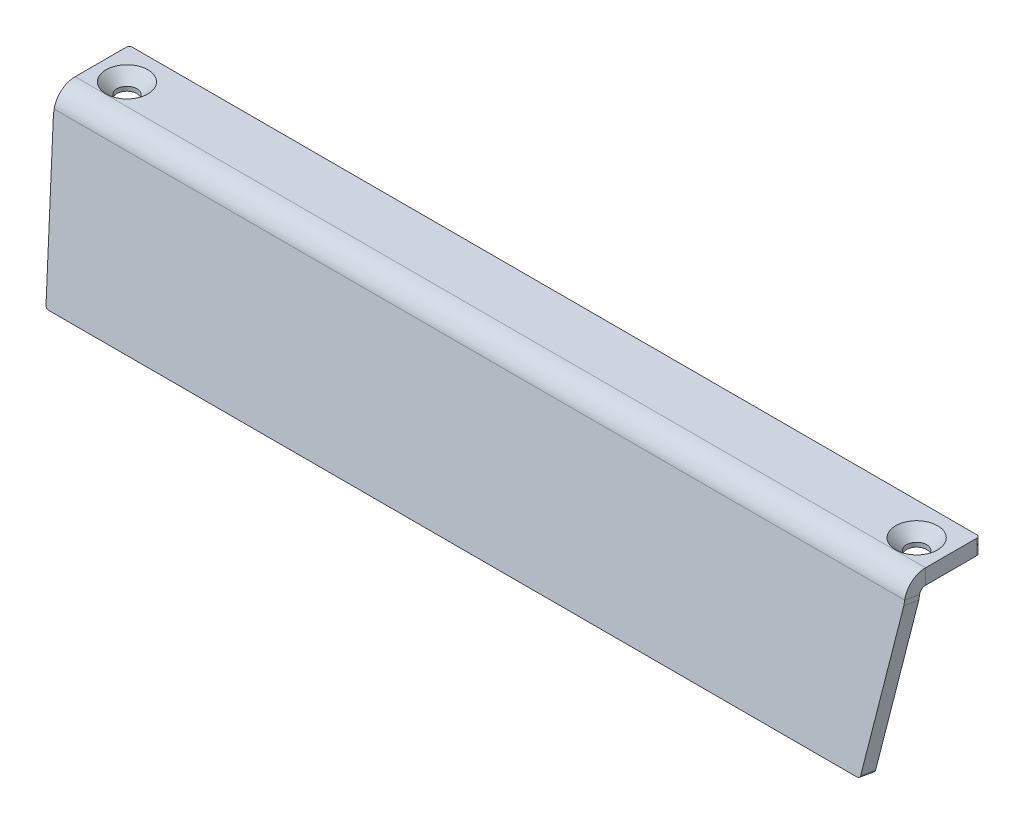
SolidWorks part; units mm, degrees
note: '?' marks a value the reader was unsure of. The reader was unsure of these and kept them because the rebuilt part matched: thickness of "Base-Flange1", "Edge-Flange1", "Sheet-Metal(1)", "Sheet-Metal(2)", "Sheet-Metal(10)", "Sheet-Metal(11)", "Sheet-Metal(12)"; flange length of "Edge-Flange1".
ref_plane "Front" through (0, 0, 0) normal (0, 0, 1) x (1, 0, 0)
ref_plane "Top" through (0, 0, 0) normal (0, 1, 0) x (1, 0, 0)
ref_plane "Right" through (0, 0, 0) normal (1, 0, 0) x (0, 0, -1)
sketch "Sketch1" plane through (0, 0, 0) normal (0, 1, 0) x (1, 0, 0)
  line L0 (-50, 0) -> (50, 0) construction
  line L1 (-70, 0) -> (70, 0)
  line L2 (-70, 0) -> (-70, -8.92)
  line L3 (-70, -8.92) -> (70, -8.92)
  line L4 (70, 0) -> (70, -8.92)
  line L5 (0, 0) -> (0, -26.7104) construction
  line L6 (0, -50) -> (0, 50) construction
  dimension "D1" = 8.92
  dimension "D2" = 140
base flange "Base-Flange1" sketch "Sketch1" thickness 2.5 reverse thickness direction no parameters "D1"=1.524
edge flange "Edge-Flange1" sketch "Sketch8" flange angle 100 flange length 26 flange position bend outside bend radius 1 thickness 2.5 relief rectangular parameters "D6"=10
sketch "Sketch8" plane through (0, -2.5, 8.92) normal (0, 0.1736, 0.9848) x (-1, 0, 0)
  line L0 (70, 0) -> (-70, 0) construction
  line L1 (70, 0) -> (-70, 0)
  line L2 (-70, 0) -> (-70, 26)
  line L3 (-70, 26) -> (70, 26)
  line L4 (70, 26) -> (70, 0)
bend "EdgeBend1" bend radius 1 bend angle 80 parameters "D5"=1
sketch "Sketch21" plane through (0, 0, 0) normal (0, 1, 0) x (1, 0, 0)
  line L0 (0, 0) -> (0, -13.0774) construction
  line L1 (0, -50) -> (0, 50) construction
  line L2 (-65, -5.39) -> (65, -5.39) construction
  circle A0 centre (-65, -5.39) radius 1.65
  circle A1 centre (65, -5.39) radius 1.65
  dimension "D1" = 3.3
  dimension "D2" = 130
  dimension "D3" = 5.39
ref_plane "Plane1" through (65, 0, 0) normal (1, 0, 0) x (0, 0, -1)
extrude "Cut-Extrude1" cut sketch "Sketch21" against normal through all normal cut yes
ref_axis "Axis2" through (65, -2.5, 5.39) along (0, 1, 0)?
sketch "Sketch24" plane through (65, 0, 0) normal (1, 0, 0) x (0, 0, -1)
  line L0 (-5.39, 0) -> (-5.39, 4.9908) construction
  line L1 (-8.92, 0) -> (0, 0) construction
  line L2 (-5.39, 0) -> (-5.39, -1.8)
  line L3 (-5.39, -1.8) -> (-3.74, -1.8)
  line L4 (-3.74, -1.8) -> (-1.94, 0)
  line L5 (-1.94, 0) -> (-5.39, 0)
  dimension "D1" = 5.39
  dimension "D2" = 45
  dimension "D3" = 1.8
  dimension "D4" = 1.65
revolve "Cut-Revolve2" cut sketch "Sketch24" angle 360 about L0
mirror "Mirror2" about plane through (0, 0, 0) normal (1, 0, 0) of "Cut-Revolve2"
chamfer "Chamfer1" distance 3 angle 83 2 edges at (-70, -27.8879, 15.505) (70, -27.8879, 15.505) first distance on face at (0, -27.8879, 15.505)
fillet "Fillet1" radius 0.5 4 edges at (-67, -27.8879, 15.505) (67, -27.8879, 15.505) (-70, -1.25, 0) (70, -1.25, 0)
sketch "Bend-Lines1" [suppressed] plane through (0, 0, 0) normal (0, 1, 0) x (1, 0, 0)
sketch "Bounding-Box1" [suppressed] plane through (0, 0, 0) normal (0, 1, 0) x (1, 0, 0)
sheet metal parameters "Sheet-Metal(1)" thickness 2.5 parameters "D1"=1.524
flat pattern "Flat-Pattern(1)" [suppressed]
sketch "Bend-Lines2" plane through (0, 0, 0) normal (0, 1, 0) x (1, 0, 0)
sketch "Bounding-Box2" [suppressed] plane through (0, 0, 0) normal (0, 1, 0) x (1, 0, 0)
sheet metal parameters "Sheet-Metal(2)" thickness 2.5 parameters "D1"=1.524, "D7"=1
flat pattern "Flat-Pattern(1)"
sketch "Bend-Lines2" plane through (0, 0, 0) normal (0, 1, 0) x (1, 0, 0)
  line L0 (-70, -9.682) -> (70, -9.682) construction
  line L1 (-70, -9.682) -> (70, -9.682) construction
sketch3d "Bounding-Box2" [suppressed]
  line L0 (70, -35.6049, 0) -> (-70, -35.6049, 0) construction
  line L1 (70, 0, 0) -> (-70, 0, 0) construction
  line L2 (70, -35.6049, 0) -> (70, 0, 0) construction
  line L3 (-70, -35.6049, 0) -> (-70, 0, 0) construction
bend of the flat pattern "Flatten-<EdgeBend1>1"
sheet metal parameters "Sheet-Metal(10)" thickness 2.5 parameters "D1"=1.524, "D7"=1
flat pattern "Flat-Pattern(1)"
sketch "Bend-Lines2" plane through (0, 0, 0) normal (0, 1, 0) x (1, 0, 0)
  line L0 (-70, -9.682) -> (70, -9.682) construction
  line L1 (-70, -9.682) -> (70, -9.682) construction
sketch3d "Bounding-Box2" [suppressed]
  line L0 (70, -35.6049, 0) -> (-70, -35.6049, 0) construction
  line L1 (70, 0, 0) -> (-70, 0, 0) construction
  line L2 (70, -35.6049, 0) -> (70, 0, 0) construction
  line L3 (-70, -35.6049, 0) -> (-70, 0, 0) construction
bend of the flat pattern "Flatten-<EdgeBend1>1"
sheet metal parameters "Sheet-Metal(11)" thickness 2.5 parameters "D1"=1.524, "D7"=1
flat pattern "Flat-Pattern(1)"
sketch "Bend-Lines2" plane through (0, 0, 0) normal (0, 1, 0) x (1, 0, 0)
sketch "Bounding-Box2" [suppressed] plane through (0, 0, 0) normal (0, 1, 0) x (1, 0, 0)
bend of the flat pattern "Flatten-<EdgeBend1>1"
sheet metal parameters "Sheet-Metal(12)" thickness 2.5 parameters "D1"=1.524, "D7"=1
flat pattern "Flat-Pattern(1)"
sketch "Bend-Lines2" plane through (0, 0, 0) normal (0, 1, 0) x (1, 0, 0)
  line L0 (-70, -9.682) -> (70, -9.682) construction
  line L1 (-70, -9.682) -> (70, -9.682) construction
sketch "Bounding-Box2" [suppressed] plane through (0, 0, 0) normal (0, 1, 0) x (1, 0, 0)
bend of the flat pattern "Flatten-<EdgeBend1>1"
